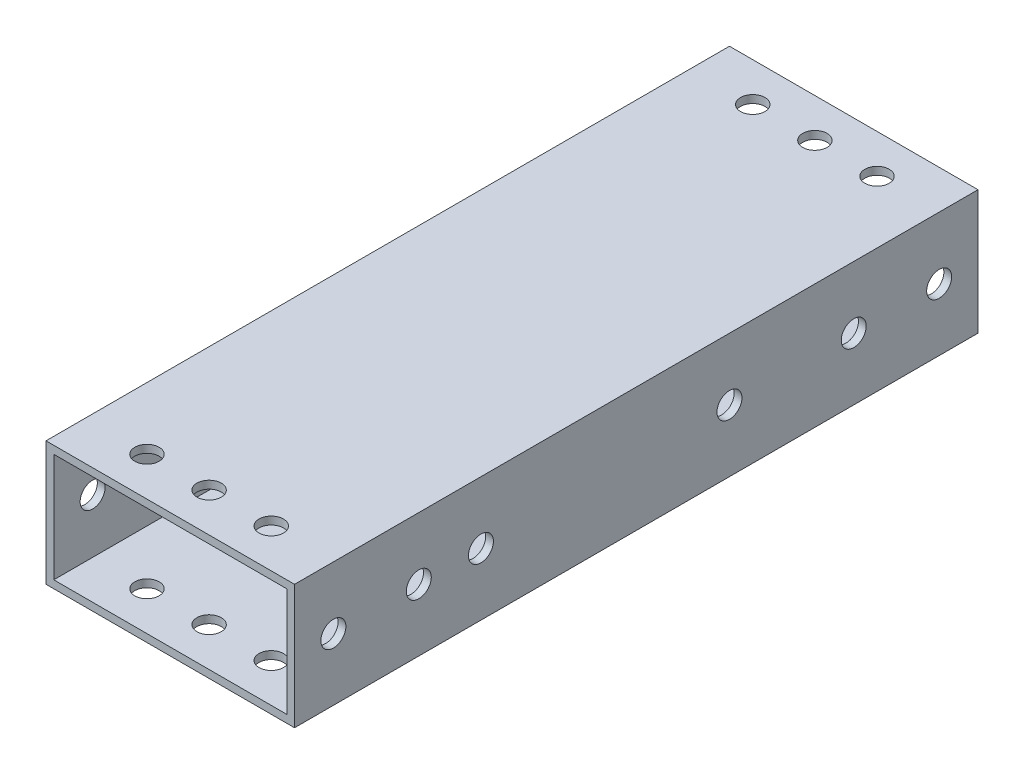
SolidWorks part; units mm, degrees
material "6061-T6 (SS)"
ref_plane "Front Plane" through (0, 0, 0) normal (0, 0, 1) x (1, 0, 0)
ref_plane "Top Plane" through (0, 0, 0) normal (0, 1, 0) x (1, 0, 0)
ref_plane "Right Plane" through (0, 0, 0) normal (1, 0, 0) x (0, 0, -1)
sketch "Sketch1" plane through (0, 0, 0) normal (0, 0, 1) x (1, 0, 0)
  line L0 (-23.8125, 11.1125) -> (23.8125, 11.1125)
  line L1 (-25.4, -12.7) -> (25.4, -12.7)
  line L2 (-25.4, -12.7) -> (-25.4, 12.7)
  line L3 (-25.4, 12.7) -> (25.4, 12.7)
  line L4 (25.4, -12.7) -> (25.4, 12.7)
  line L5 (-25.4, -12.7) -> (25.4, 12.7) construction
  line L6 (-25.4, 12.7) -> (25.4, -12.7) construction
  line L7 (23.8125, -11.1125) -> (23.8125, 11.1125)
  line L8 (-23.8125, -11.1125) -> (23.8125, -11.1125)
  line L9 (-23.8125, -11.1125) -> (-23.8125, 11.1125)
  point P0 (0, 0)
  dimension "D1" = 50.8
  dimension "D2" = 25.4
  dimension "D3" = 1.5875
extrude "Boss-Extrude1" add sketch "Sketch1" along normal mid plane 139.7
sketch "Sketch2" plane through (0, 12.7, 0) normal (0, 1, 0) x (1, 0, 0)
  line L0 (25.4, 69.85) -> (-25.4, 69.85) construction
  line L1 (25.4, 0) -> (-25.4, 0) construction
  line L2 (25.4, -69.85) -> (25.4, 69.85) construction
  line L3 (-25.4, -69.85) -> (-25.4, 69.85) construction
  circle A0 centre (-12.7, 61.9125) radius 2.4892
  circle A1 centre (0, 61.9125) radius 2.4892
  circle A2 centre (12.7, 61.9125) radius 2.4892
  circle A3 centre (12.7, -61.9125) radius 2.4892
  circle A4 centre (0, -61.9125) radius 2.4892
  circle A5 centre (-12.7, -61.9125) radius 2.4892
  dimension "D4" = 4.9784
  dimension "D1" = 12.7
  dimension "D2" = 12.7
  dimension "D3" = 7.9375
extrude "Cut-Extrude1" cut sketch "Sketch2" against normal through all
sketch "Sketch3" plane through (-25.4, 0, 0) normal (-1, 0, 0) x (0, 0, 1)
  line L0 (-69.85, 12.7) -> (-69.85, -12.7) construction
  line L1 (0, 12.7) -> (0, -12.7) construction
  line L2 (69.85, 12.7) -> (-69.85, 12.7) construction
  line L3 (69.85, -12.7) -> (-69.85, -12.7) construction
  line L4 (69.85, 12.7) -> (69.85, -12.7) construction
  circle A0 centre (-61.9125, 0) radius 2.5527
  circle A1 centre (61.9125, 0) radius 2.5527
  circle A4 centre (31.75, 0) radius 2.5527
  circle A5 centre (44.45, 0) radius 2.5527
  dimension "D1" = 5.1054
  dimension "D3" = 12.7
  dimension "D4" = 25.4
  dimension "D2" = 7.9375
extrude "Cut-Extrude2" cut sketch "Sketch3" against normal through all contours A5 | A1 | A4 | A0
sketch "Sketch5" plane through (25.4, 0, 0) normal (1, 0, 0) x (0, 0, -1)
  line L0 (69.85, -12.7) -> (69.85, 12.7) construction
  circle A1 centre (44.45, 0) radius 2.5527
  circle A2 centre (19.05, 0) radius 2.5527
  dimension "D1" = 25.4
  dimension "D3" = 5.1054
  dimension "D4" = 25.4
extrude "Cut-Extrude3" cut sketch "Sketch5" against normal through all
